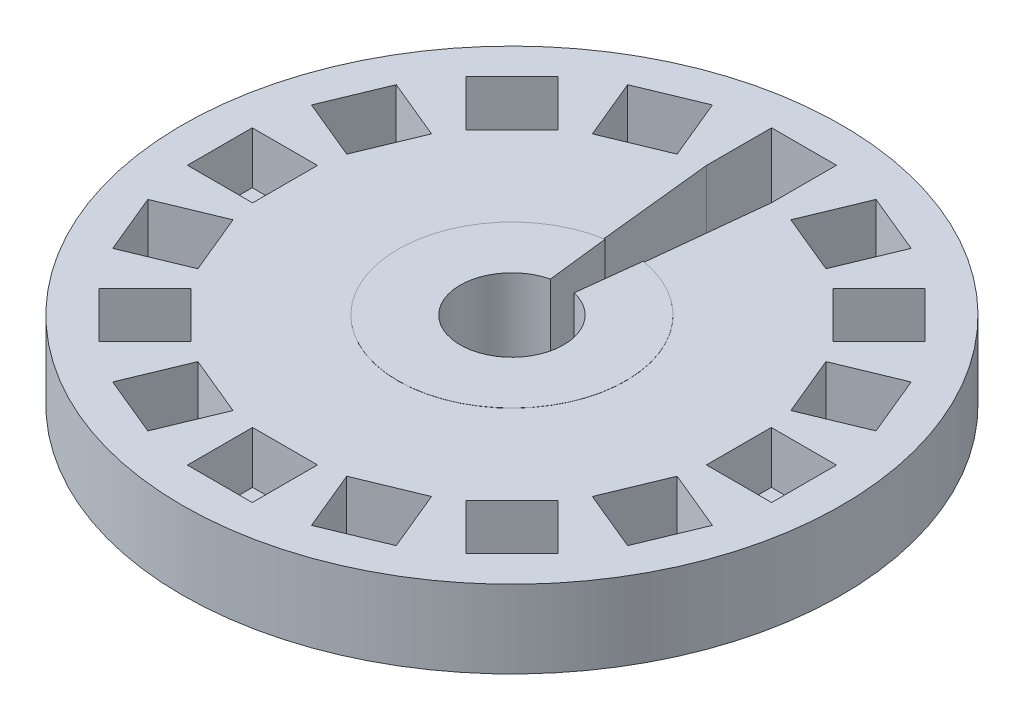
SolidWorks part; units mm, degrees
ref_plane "Front Plane" through (0, 0, 0) normal (0, 0, 1) x (1, 0, 0)
ref_plane "Top Plane" through (0, 0, 0) normal (0, 1, 0) x (1, 0, 0)
ref_plane "Right Plane" through (0, 0, 0) normal (1, 0, 0) x (0, 0, -1)
sketch "Sketch1" plane through (0, 0, 0) normal (0, 1, 0) x (1, 0, 0)
  circle A0 centre (0, 0) radius 63.5
  dimension "D1" = 127
extrude "Boss-Extrude1" add sketch "Sketch1" along normal blind 14.9734
sketch "Sketch2" plane through (0, 14.9734, 0) normal (0, 1, 0) x (1, 0, 0)
  line L0 (0, 0) -> (0, -50) construction
  line L1 (-6.25, -56.28) -> (6.25, -56.28)
  line L2 (-6.25, -56.28) -> (-6.25, -43.72)
  line L3 (-6.25, -43.72) -> (6.25, -43.72)
  line L4 (6.25, -56.28) -> (6.25, -43.72)
  line L5 (-6.25, -56.28) -> (6.25, -43.72) construction
  line L6 (-6.25, -43.72) -> (6.25, -56.28) construction
  point P0 (0, -50)
  dimension "D1" = 12.5
  dimension "D2" = 12.56
  dimension "D3" = 50
extrude "Cut-Extrude1" cut sketch "Sketch2" against normal blind 10
pattern_circular "CirPattern1" count 16 over 360 about axis through (0, 14.9734, 0) along (0, -1, 0) of "Cut-Extrude1"
sketch "Sketch5" plane through (0, 0, 0) normal (0, 1, 0) x (1, 0, 0)
  line L0 (-56.28, 0) -> (-63.5, 0) construction
  line L1 (-56.28, 6.25) -> (-56.28, -6.25) construction
  line L3 (-6.25, 56.28) -> (6.25, 56.28)
  line L4 (-6.25, 56.28) -> (-6.25, 43.72)
  line L5 (-6.25, 43.72) -> (6.25, 43.72)
  line L6 (6.25, 56.28) -> (6.25, 43.72)
  circle A0 centre (0, 0) radius 63.5 construction
extrude "Cut-Extrude3" cut sketch "Sketch5" against normal blind 31 and the other way blind 37
sketch "Sketch6" plane through (0, 14.9734, 0) normal (0, 1, 0) x (1, 0, 0)
  circle A0 centre (0, 0) radius 17.6259
extrude "Cut-Extrude4" cut sketch "Sketch6" against normal blind 37 and the other way blind 26 contours A0
sketch "Sketch7" plane through (0, 0, 0) normal (0, 1, 0) x (1, 0, 0)
  line L5 (0, 43.72) -> (0, 0) construction
  line L6 (-6.25, 43.72) -> (6.25, 43.72) construction
sketch "Sketch8" plane through (0, 0, 0) normal (0, 1, 0) x (1, 0, 0)
sketch "Sketch9" plane through (0, 0, 0) normal (0, 1, 0) x (1, 0, 0)
  line L0 (-6.25, 43.72) -> (0, -15.0986)
  line L1 (0, -15.0986) -> (6.25, 43.72)
  line L2 (6.25, 43.72) -> (-6.25, 43.72)
extrude "Cut-Extrude9" cut sketch "Sketch9" against normal blind 11 and the other way blind 19
sketch "Sketch12" plane through (-6.25, 0, 0) normal (1, 0, 0) x (0, 0, -1)
  line L0 (56.28, 14.9734) -> (56.28, 9.9734) construction
  line L1 (56.28, 0) -> (56.28, 14.9734) construction
  line L2 (56.28, 9.9734) -> (18.4333, -3.0647)
  line L3 (18.4333, -3.0647) -> (18.4333, -10.1043)
  line L4 (18.4333, -10.1043) -> (54.4658, 0)
  line L5 (54.4658, 0) -> (56.28, 9.9734)
sketch "Sketch13" plane through (0, 0, 0) normal (0, 1, 0) x (1, 0, 0)
  circle A0 centre (0, 0) radius 21.9529
extrude "Boss-Extrude4" add sketch "Sketch13" against normal blind 18 and the other way blind 15
sketch "Sketch16" plane through (0, 0, 0) normal (0, 1, 0) x (1, 0, 0)
  circle A0 centre (0, 0) radius 9.9764
extrude "Cut-Extrude11" cut sketch "Sketch16" against normal blind 29 and the other way blind 33
sketch "Sketch17" plane through (0, 0, 0) normal (0, 1, 0) x (1, 0, 0)
  line L0 (-6.25, 43.72) -> (0, -9.9764)
  line L1 (-6.25, 56.28) -> (6.25, 56.28) construction
  line L2 (-6.25, 56.28) -> (-6.25, 43.72) construction
  line L3 (-6.25, 43.72) -> (6.25, 43.72) construction
  line L4 (6.25, 56.28) -> (6.25, 43.72) construction
  line L5 (-6.25, 56.28) -> (6.25, 43.72) construction
  line L6 (-6.25, 43.72) -> (6.25, 56.28) construction
  line L7 (0, -9.9764) -> (6.25, 43.72)
  line L8 (6.25, 43.72) -> (-6.25, 43.72)
  circle A0 centre (0, 0) radius 9.9764 construction
  point P4 (0, 50)
extrude "Cut-Extrude15" cut sketch "Sketch17" against normal blind 29 and the other way blind 27 contours L8 L0 L7
equation "\"line\"= 5"
equation "\"D3@Sketch2\"=\"line\""
